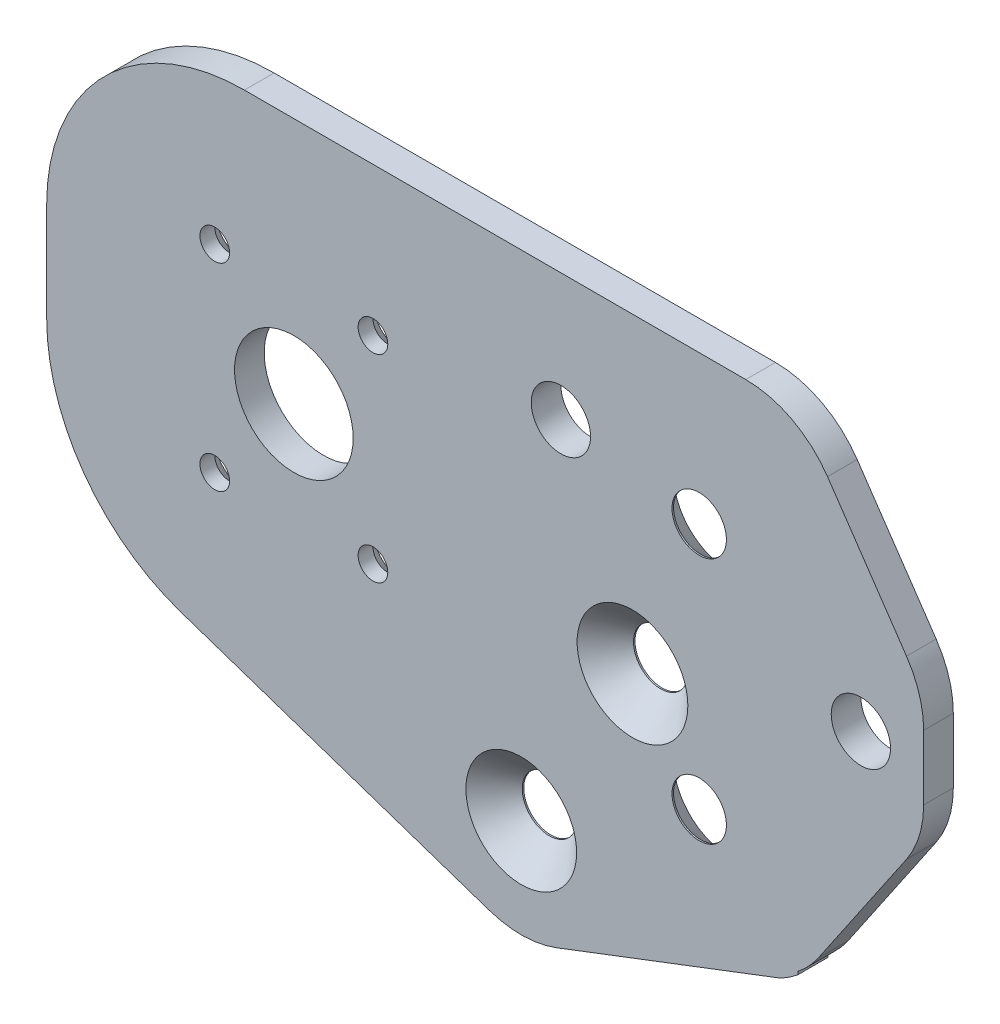
SolidWorks part; units mm, degrees
material "Gerais  - 6061-T6"
ref_plane "Plano frontal" through (0, 0, 0) normal (0, 0, 1) x (1, 0, 0)
ref_plane "Plano superior" through (0, 0, 0) normal (0, 1, 0) x (1, 0, 0)
ref_plane "Plano direito" through (0, 0, 0) normal (1, 0, 0) x (0, 0, -1)
sketch "Esboço1" plane through (0, 0, 0) normal (0, 0, 1) x (1, 0, 0)
  line L0 (56, 50) -> (56, 0) construction
  line L1 (0, 0) -> (76, 0)
  line L2 (0, 0) -> (0, 50)
  line L3 (0, 50) -> (76, 50)
  line L4 (76, 0) -> (76, 50)
  line L5 (66, 50) -> (66, 18.5) construction
  line L6 (65.25, 50) -> (65.25, 18.5) construction
  line L7 (59.25, 12.5) -> (25, 12.5) construction
  circle A0 centre (25, 25) radius 16 construction
  circle A1 centre (59.25, 18.5) radius 9.75 construction
  circle A2 centre (59.25, 18.5) radius 6 construction
  circle A3 centre (25, 25) radius 12.5 construction
  circle A4 centre (59.25, 18.5) radius 2.5
  circle A5 centre (25, 25) radius 6
  circle A6 centre (17, 38.8564) radius 1.5 construction
  circle A7 centre (33, 38.8564) radius 1.5 construction
  circle A8 centre (41, 25) radius 1.5 construction
  circle A9 centre (33, 11.1436) radius 1.5 construction
  circle A10 centre (17, 11.1436) radius 1.5 construction
  circle A11 centre (9, 25) radius 1.5 construction
  point P7 (41, 25)
  point P36 (25, 25)
  dimension "D1" = 32
  dimension "D5" = 12
  dimension "D6" = 19.5
  dimension "D9" = 25
  dimension "D10" = 5
  dimension "D13" = 12
  dimension "D14" = 3
  dimension "D2" = 25
  dimension "D3" = 35
  dimension "D4" = 20
  dimension "D7" = 0.75
  dimension "D8" = 10
  dimension "D11" = 25
  dimension "D12" = 50
  dimension "D15" = 6
extrude "Ressalto-extrusão1" add sketch "Esboço1" along normal blind 3
sketch "Esboço2" plane through (0, 0, 3) normal (0, 0, 1) x (1, 0, 0)
  line L0 (66, 50) -> (66, 0) construction
  line L1 (76, 50) -> (0, 50) construction
  line L2 (0, 0) -> (76, 0) construction
  line L3 (76, 0) -> (76, 50) construction
  circle A0 centre (66, 35) radius 2.5
  circle A1 centre (66, 10) radius 2.5
  dimension "D2" = 5
  dimension "D3" = 5
  dimension "D1" = 10
  dimension "D4" = 10
  dimension "D5" = 15
extrude "Corte-extrusão1" cut sketch "Esboço2" against normal blind 3
fillet "Filete1" radius 20 2 edges at (0, 0, 1.5) (0, 50, 1.5)
sketch "Esboço3" plane through (0, 0, 3) normal (0, 0, 1) x (1, 0, 0)
  line L1 (17, 15) -> (33, 15) construction
  line L2 (17, 15) -> (17, 35) construction
  line L3 (17, 35) -> (33, 35) construction
  line L4 (33, 15) -> (33, 35) construction
  line L5 (17, 15) -> (33, 35) construction
  line L6 (17, 35) -> (33, 15) construction
  circle A0 centre (33, 35) radius 1.5
  circle A1 centre (33, 15) radius 1.5
  circle A2 centre (17, 15) radius 1.5
  circle A3 centre (17, 35) radius 1.5
  point P0 (25, 25)
  dimension "D3" = 3
  dimension "D1" = 20
  dimension "D2" = 16
extrude "Corte-extrusão2" cut sketch "Esboço3" against normal through all
sketch "Esboço4" plane through (0, 0, 3) normal (0, 0, 1) x (1, 0, 0)
  line L0 (76, 50) -> (20, 50) construction
  line L1 (55.3323, 43.65) -> (51.6662, 50) construction
  line L2 (51.6662, 50) -> (44.3338, 50) construction
  line L3 (44.3338, 50) -> (40.6677, 43.65) construction
  line L4 (40.6677, 43.65) -> (44.3338, 37.3) construction
  line L5 (44.3338, 37.3) -> (51.6662, 37.3) construction
  line L6 (51.6662, 37.3) -> (55.3323, 43.65) construction
  line L7 (76, 0) -> (76, 50) construction
  line L8 (76, 0) -> (76, 50) construction
  line L9 (51.4498, -6.4701) -> (55.3282, -0.2474) construction
  line L10 (55.3282, -0.2474) -> (51.8783, 6.2227) construction
  line L11 (51.8783, 6.2227) -> (44.5502, 6.4701) construction
  line L12 (44.5502, 6.4701) -> (40.6718, 0.2474) construction
  line L13 (40.6718, 0.2474) -> (44.1217, -6.2227) construction
  line L14 (44.1217, -6.2227) -> (51.4498, -6.4701) construction
  line L15 (25, 12.5) -> (61.6574, 12.5) construction
  line L16 (20, 0) -> (76, 0) construction
  line L17 (48, 43.65) -> (48, 0) construction
  circle A0 centre (48, 43.65) radius 3 construction
  circle A1 centre (48, 43.65) radius 6.35 construction
  circle A2 centre (48, 0) radius 2.5
  circle A3 centre (48, 0) radius 6.35 construction
  arc A4 (17.8926, 14.7172) -> (30.3514, 13.7035) centre (25, 25) ccw construction
  arc A5 (17.8926, 14.7172) -> (30.3514, 13.7035) centre (25, 25) ccw construction
  circle A6 centre (52.0071, 37.1424) radius 3
  circle A7 centre (25, 25) radius 29.6112 construction
  circle A8 centre (59.25, 18.5) radius 2.5 construction
  point P34 (54.6112, 32.9034)
  point P35 (53.7637, 32.0336)
  dimension "D1" = 12.7
  dimension "D3" = 6
  dimension "D4" = 5
  dimension "D6" = 20
  dimension "D2" = 28
  dimension "D5" = 28
extrude "Corte-extrusão3" cut sketch "Esboço4" against normal through all
sketch "Esboço5" plane through (0, 0, 0) normal (0, 0, -1) x (-1, 0, 0)
  line L0 (-76, 0) -> (-51.5714, -9.3405)
  line L1 (-44.8034, -9.4753) -> (-13.6067, 1.0494)
  line L2 (-20, 0) -> (-45.5, 0) construction
  line L3 (-50.5, 0) -> (-76, 0) construction
  line L4 (-20, 0) -> (-45.5, 0)
  line L5 (-50.5, 0) -> (-76, 0)
  circle A0 centre (-48, 0) radius 2.5
  arc A1 (-51.5714, -9.3405) -> (-44.8034, -9.4753) centre (-48, 0) ccw
  arc A2 (-20, 0) -> (0, 20) centre (-20, 20) ccw construction
  line M5 (-45.5, 0) -> (-20, 0)
  arc M6 (-20, 0) -> (0, 20) centre (-20, 20) ccw
  line M11 (-76, 0) -> (-50.5, 0)
  dimension "D1" = 20
extrude "Ressalto-extrusão2" add sketch "Esboço5" against normal through all contours L0 A1 L1 A0 M6 M5 M11 region at (46.8798, -3.5834, 0)
sketch "Esboço6" plane through (0, 0, 0) normal (0, 0, -1) x (-1, 0, 0)
  line L7 (-86.9656, 16.103) -> (-78.0603, 3.0256)
  line L8 (-72.4733, -0.9805) -> (-50.0089, -7.2259)
  line L9 (-46.1556, -7.2697) -> (-15.0816, 0.6142)
  line L10 (0, 20) -> (0, 30)
  line L11 (-20, 50) -> (-70.7112, 50)
  line L12 (-78.9768, 45.6286) -> (-86.9656, 33.897)
  line L13 (-88.7, 28.2685) -> (-88.7, 21.7315)
  line L14 (-86.9656, 16.103) -> (-78.0603, 3.0256)
  line L15 (-72.4733, -0.9805) -> (-50.0089, -7.2259)
  line L16 (-46.1556, -7.2697) -> (-15.0816, 0.6142)
  line L17 (0, 20) -> (0, 30)
  line L18 (-20, 50) -> (-70.7112, 50)
  line L19 (-78.9768, 45.6286) -> (-86.9656, 33.897)
  line L20 (-88.7, 28.2685) -> (-88.7, 21.7315)
  circle A0 centre (-82.35, 25) radius 3 construction
  circle A1 centre (-82.35, 25) radius 3
  arc A7 (-78.0603, 3.0256) -> (-72.4733, -0.9805) centre (-69.7947, 8.6541) ccw
  arc A8 (-50.0089, -7.2259) -> (-46.1556, -7.2697) centre (-48, 0) ccw
  arc A9 (-15.0816, 0.6142) -> (0, 20) centre (-20, 20) ccw
  arc A10 (0, 30) -> (-20, 50) centre (-20, 30) ccw
  arc A11 (-70.7112, 50) -> (-78.9768, 45.6286) centre (-70.7112, 40) ccw
  arc A12 (-86.9656, 33.897) -> (-88.7, 28.2685) centre (-78.7, 28.2685) ccw
  arc A13 (-88.7, 21.7315) -> (-86.9656, 16.103) centre (-78.7, 21.7315) ccw
  arc A15 (-50.0089, -7.2259) -> (-46.1556, -7.2697) centre (-48, 0) ccw
  arc A16 (-15.0816, 0.6142) -> (0, 20) centre (-20, 20) ccw
  arc A17 (0, 30) -> (-20, 50) centre (-20, 30) ccw
  arc A18 (-70.7112, 50) -> (-78.9768, 45.6286) centre (-70.7112, 40) ccw
  arc A19 (-86.9656, 33.897) -> (-88.7, 28.2685) centre (-78.7, 28.2685) ccw
  arc A20 (-88.7, 21.7315) -> (-86.9656, 16.103) centre (-78.7, 21.7315) ccw
  arc A54 (-78.0603, 3.0256) -> (-72.4733, -0.9805) centre (-69.7947, 8.6541) ccw
  line M16 (-76, 50) -> (-76, 0)
  dimension "D1" = 0
extrude "Ressalto-extrusão3" add sketch "Esboço6" against normal through all contours L20 A20 L14 A54 A18 L19 A19 A1 M16 region at (87.7851, 18.9319, 0)
sketch "Esboço7" plane through (0, 0, 0) normal (0, 0, -1) x (-1, 0, 0)
  line L0 (-76, 0) -> (-51.5714, -9.3405) construction
  line L9 (-76, 0.8122) -> (-76, 0)
  line L10 (-76, 0) -> (-51.5714, -9.3405)
  line L11 (-44.8034, -9.4753) -> (-13.6067, 1.0494)
  line L12 (0, 20) -> (0, 30)
  line L13 (-20, 50) -> (-76, 50)
  line L15 (-78.9768, 45.6286) -> (-86.9656, 33.897)
  line L16 (-88.7, 28.2685) -> (-88.7, 21.7315)
  line L17 (-86.9656, 16.103) -> (-78.0603, 3.0256)
  line L18 (-76, 0.8122) -> (-76, 0)
  line L19 (-76, 0) -> (-51.5714, -9.3405)
  line L20 (-44.8034, -9.4753) -> (-13.6067, 1.0494)
  line L21 (0, 20) -> (0, 30)
  line L22 (-20, 50) -> (-76, 50)
  line L24 (-78.9768, 45.6286) -> (-86.9656, 33.897)
  line L25 (-88.7, 28.2685) -> (-88.7, 21.7315)
  line L26 (-86.9656, 16.103) -> (-78.0603, 3.0256)
  line L27 (-76, 50) -> (-76, 48.487)
  line L28 (-76, 50) -> (-76, 48.487)
  arc A0 (-78.9768, 45.6286) -> (-70.7112, 50) centre (-70.7112, 40) cw
  arc A1 (-78.0603, 3.0256) -> (-72.5961, -1.3015) centre (-70.1034, 7.4599) ccw
  arc A7 (-51.5714, -9.3405) -> (-44.8034, -9.4753) centre (-48, 0) ccw
  arc A8 (-13.6067, 1.0494) -> (0, 20) centre (-20, 20) ccw
  arc A9 (0, 30) -> (-20, 50) centre (-20, 30) ccw
  arc A10 (-76, 48.487) -> (-78.9768, 45.6286) centre (-70.7112, 40) ccw
  arc A11 (-86.9656, 33.897) -> (-88.7, 28.2685) centre (-78.7, 28.2685) ccw
  arc A12 (-88.7, 21.7315) -> (-86.9656, 16.103) centre (-78.7, 21.7315) ccw
  arc A14 (-51.5714, -9.3405) -> (-44.8034, -9.4753) centre (-48, 0) ccw
  arc A15 (-13.6067, 1.0494) -> (0, 20) centre (-20, 20) ccw
  arc A16 (0, 30) -> (-20, 50) centre (-20, 30) ccw
  arc A17 (-76, 48.487) -> (-78.9768, 45.6286) centre (-70.7112, 40) ccw
  arc A18 (-86.9656, 33.897) -> (-88.7, 28.2685) centre (-78.7, 28.2685) ccw
  arc A19 (-88.7, 21.7315) -> (-86.9656, 16.103) centre (-78.7, 21.7315) ccw
  arc A22 (-78.0603, 3.0256) -> (-76, 0.8122) centre (-69.7947, 8.6541) ccw
  arc A23 (-78.0603, 3.0256) -> (-76, 0.8122) centre (-69.7947, 8.6541) ccw
  line M18 (-76, 0.8122) -> (-76, 0)
  line M19 (-76, 0) -> (-51.5714, -9.3405)
  line M26 (-76, 50) -> (-76, 48.487)
  dimension "D1" = 0
extrude "Corte-extrusão4" cut sketch "Esboço7" against normal through all contours A1 M18 M19 | A0 L22 M26 region at (75.4496, -0.0541, 0) region at (74.6987, 49.5527, 0)
chamfer "Chanfro1" distance 1.5 angle 45 4 edges at (18.5, 35, 0) (18.5, 15, 0) (34.5, 15, 0) (34.5, 35, 0)
hole_wizard "Escareado para SFHCS M51" positions "Esboço16" profile "Esboço17" countersink size "M5" standard "Ansi Metric" end condition through all
sketch "Esboço16" plane through (0, 0, 3) normal (0, 0, 1) x (1, 0, 0)
  point P0 (48, 0)
sketch "Esboço17" plane through (48, 0, 3) normal (1, 0, 0) x (0, -1, 0)
  line L0 (0, 0) -> (0, 3)
  line L1 (0, 3) -> (2.75, 3)
  line L2 (2.75, 3) -> (2.75, 2.85)
  line L3 (2.75, 2.85) -> (5.6, 0)
  line L5 (5.6, 0) -> (0, 0)
  line L6 (-2.75, 2.85) -> (-5.6, 0) construction
  line L11 (0, -6.35) -> (0, 107.95) construction
  dimension "Thru Hole Dia." = 5.5
  dimension "Thru Hole Depth" = 3
  dimension "Near C'Sink Dia." = 11.2
  dimension "Near C'Sink Angle" = 90
hole_wizard "Escareado para SFHCS M52" positions "Esboço18" profile "Esboço19" countersink size "M5" standard "Ansi Metric" end condition through all
sketch "Esboço18" plane through (0, 0, 3) normal (0, 0, 1) x (1, 0, 0)
  point P0 (59.25, 18.5)
sketch "Esboço19" plane through (59.25, 18.5, 3) normal (1, 0, 0) x (0, -1, 0)
  line L0 (0, 0) -> (0, 3)
  line L1 (0, 3) -> (2.75, 3)
  line L2 (2.75, 3) -> (2.75, 2.85)
  line L3 (2.75, 2.85) -> (5.6, 0)
  line L5 (5.6, 0) -> (0, 0)
  line L6 (-2.75, 2.85) -> (-5.6, 0) construction
  line L11 (0, -6.35) -> (0, 107.95) construction
  dimension "Thru Hole Dia." = 5.5
  dimension "Thru Hole Depth" = 3
  dimension "Near C'Sink Dia." = 11.2
  dimension "Near C'Sink Angle" = 90
hole_wizard "Escareado para SFHCS M54" positions "Esboço22" profile "Esboço23" countersink size "M5" standard "Ansi Metric" end condition through all
sketch "Esboço22" plane through (0, 0, 0) normal (0, 0, -1) x (-1, 0, 0)
  point P0 (-66, 35)
  point P3 (-66, 10)
sketch "Esboço23" plane through (66, 35, 0) normal (1, 0, 0) x (0, 1, 0)
  line L0 (0, 0) -> (0, 3)
  line L1 (0, 3) -> (2.75, 3)
  line L2 (2.75, 3) -> (2.75, 2.85)
  line L3 (2.75, 2.85) -> (5.6, 0)
  line L5 (5.6, 0) -> (0, 0)
  line L6 (-2.75, 2.85) -> (-5.6, 0) construction
  line L11 (0, -6.35) -> (0, 107.95) construction
  dimension "Thru Hole Dia." = 5.5
  dimension "Thru Hole Depth" = 3
  dimension "Near C'Sink Dia." = 11.2
  dimension "Near C'Sink Angle" = 90
